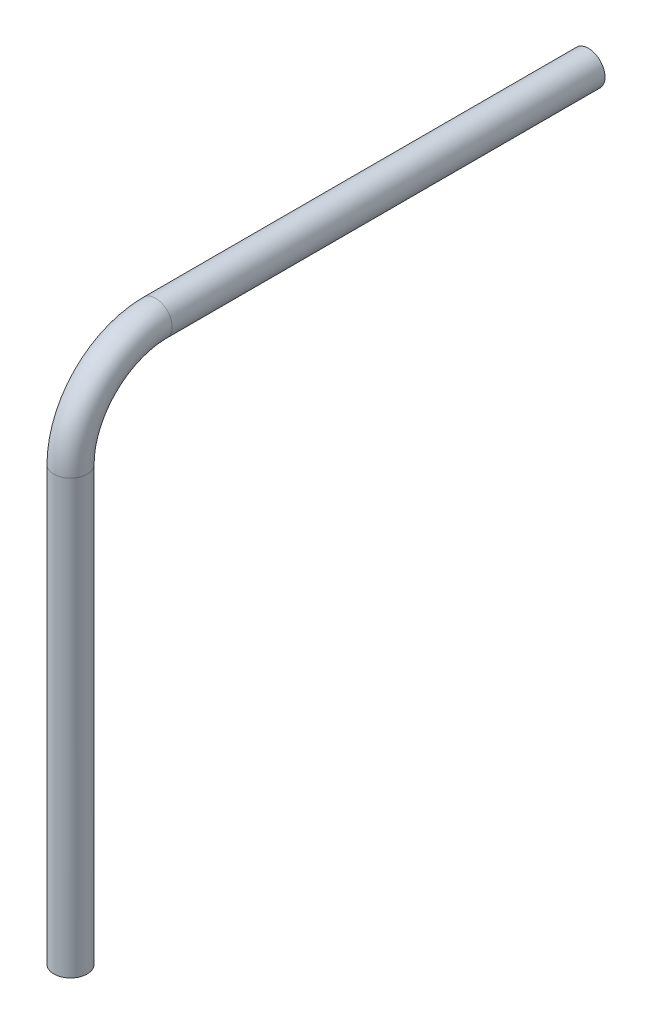
SolidWorks part; units mm, degrees
material "Cast Carbon Steel"
ref_plane "Front Plane" through (0, 0, 0) normal (0, 0, 1) x (1, 0, 0)
ref_plane "Top Plane" through (0, 0, 0) normal (0, 1, 0) x (1, 0, 0)
ref_plane "Right Plane" through (0, 0, 0) normal (1, 0, 0) x (0, 0, -1)
sketch "Sketch2" plane through (0, 0, 0) normal (1, 0, 0) x (0, 0, -1)
  arc A0 (-64.8338, 0) -> (0, 64.8338) centre (0, 0) cw
  point P4 (0, 0)
sketch "Sketch3" plane through (0, 0, 0) normal (0, 1, 0) x (1, 0, 0)
  circle A0 centre (0, -64.8338) radius 12.7
  circle A1 centre (0, -64.8338) radius 4.7625
  dimension "D1" = 25.4
  dimension "D2" = 7.9375
sweep "Sweep1" add profiles "Sketch3" path "Sketch2"
ref_plane "Plane1" through (0, 0, 0) normal (0, -1, 0) x (-1, 0, 0)
ref_plane "Plane2" through (0, 0, 0) normal (0, 0, -1) x (-1, 0, 0)
sketch "Sketch4" plane through (0, 0, 0) normal (0, -1, 0) x (-1, 0, 0)
  circle A0 centre (0, -64.8338) radius 12.7
  circle A1 centre (0, -64.8338) radius 4.7625
  dimension "D1" = 7.9375
  dimension "D2" = 25.4
extrude "Boss-Extrude3" add sketch "Sketch4" along normal blind 330.2
sketch "Sketch5" plane through (0, 0, 0) normal (0, 0, -1) x (-1, 0, 0)
  circle A2 centre (0, 64.8338) radius 4.7625
  circle A3 centre (0, 64.8338) radius 12.7
  circle A5 centre (0, 64.8338) radius 12.7 construction
  dimension "D2" = 25.4
extrude "Boss-Extrude4" add sketch "Sketch5" along normal blind 330.2
ref_plane "Plane3" through (-12.7, 0, 0) normal (-1, 0, 0) x (0, 0, 1)
sketch "Sketch6" plane through (-12.7, 0, 0) normal (-1, 0, 0) x (0, 0, 1)
  line L0 (52.1338, 0) -> (77.5338, 0) construction
  line L1 (57.15, -152.4) -> (69.85, -152.4)
  line L2 (57.15, -152.4) -> (57.15, 0)
  line L3 (57.15, 0) -> (69.85, 0)
  line L4 (69.85, -152.4) -> (69.85, 0)
  point P12 (63.5, -152.4)
  point P13 (63.5, -152.4)
  dimension "D1" = 57.15
  dimension "D2" = 63.5
  dimension "D3" = 152.4
extrude "Cut-Extrude1" cut sketch "Sketch6" against normal blind 6.35
